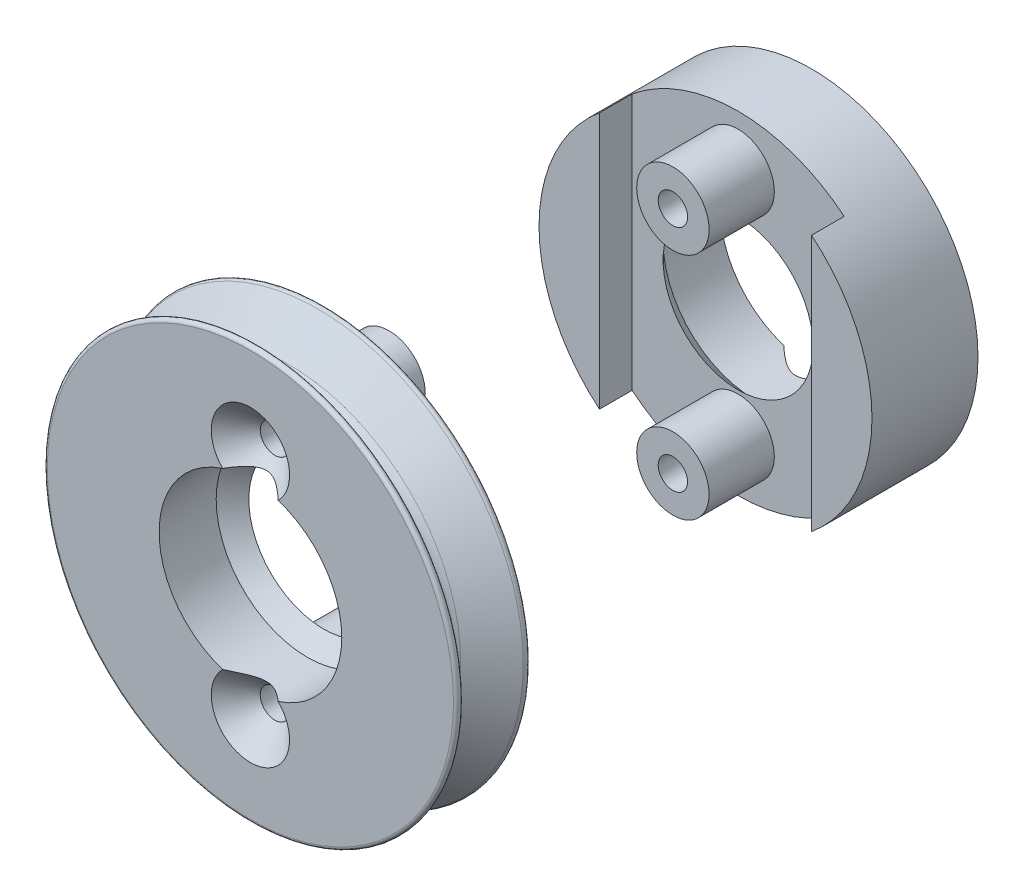
SolidWorks part; units mm, degrees
material "ABS"
ref_plane "Front Plane" through (0, 0, 0) normal (0, 0, 1) x (1, 0, 0)
ref_plane "Top Plane" through (0, 0, 0) normal (0, 1, 0) x (1, 0, 0)
ref_plane "Right Plane" through (0, 0, 0) normal (1, 0, 0) x (0, 0, -1)
sketch "Sketch2" plane through (0, 0, 0) normal (1, 0, 0) x (0, 0, -1)
  line L0 (-2, 11.2) -> (-9, 11.2)
  line L1 (-9, 11.2) -> (-9, 24.9013)
  line L2 (-8.2241, 25.0381) -> (-6.9207, 21.457)
  line L3 (-4.2129, 20.9796) -> (-0.7064, 25.1584)
  line L4 (0, 24.9013) -> (0, 9.2)
  line L6 (-2, 11.2) -> (0, 9.2)
  line L7 (0, 0) -> (7.0902, 0) construction
  arc A0 (-9, 24.9013) -> (-8.2241, 25.0381) centre (-8.6, 24.9013) cw
  arc A1 (-6.9207, 21.457) -> (-4.2129, 20.9796) centre (-5.429, 22) ccw
  arc A2 (-0.7064, 25.1584) -> (0, 24.9013) centre (-0.4, 24.9013) cw
  dimension "D1" = 11.2
  dimension "D4" = 1.5875
  dimension "D7" = 0.4
  dimension "D2" = 7
  dimension "D3" = 40
  dimension "D5" = 2
  dimension "D6" = 45
  dimension "D8" = 20
  dimension "D9" = 22
revolve "Revolve1" add sketch "Sketch2" angle 360 about L7
sketch "Sketch3" plane through (0, 0, 0) normal (0, 0, -1) x (-1, 0, 0)
  line L0 (0, 9.625) -> (0, -9.625) construction
  circle A0 centre (0, 14.0625) radius 4.4375
  circle A1 centre (0, -14.0625) radius 4.4375
  point P4 (0, 18.5)
  point P5 (0, -18.5)
  point P7 (0, -9.625)
  dimension "D1" = 19.25
  dimension "D2" = 37
extrude "Boss-Extrude1" add sketch "Sketch3" along normal blind 8
sketch "Sketch4" plane through (0, 0, -8) normal (0, 0, -1) x (-1, 0, 0)
  circle A0 centre (0, 14.0625) radius 1.8
  circle A1 centre (0, -14.0625) radius 1.8
  dimension "D1" = 3.6
extrude "Cut-Extrude1" cut sketch "Sketch4" against normal through all
chamfer "Chamfer1" distance 3 angle 45 2 edges at (-1.8, -14.0625, 9) (-1.8, 14.0625, 9)
ref_plane "Plane1" through (0, 0, -25.4) normal (0, 0, -1) x (-1, 0, 0)
mirror "Mirror2" about plane through (0, 0, -25.4) normal (0, 0, -1) of bodies 103
sketch "Sketch8" plane through (0, 0, -59.8) normal (0, 0, -1) x (-1, 0, 0)
  circle A0 centre (0, 0) radius 20.4125
  circle A1 centre (0, 0) radius 20.4125 construction
  circle A2 centre (0, 0) radius 31.2181
extrude "Cut-Extrude3" cut sketch "Sketch8" against normal blind 25
sketch "Sketch9" plane through (0, 0, -50.8) normal (0, 0, 1) x (1, 0, 0)
  line L1 (13, -35.7575) -> (-13, -35.7575)
  line L2 (13, -35.7575) -> (13, 35.7575)
  line L3 (13, 35.7575) -> (-13, 35.7575)
  line L4 (-13, -35.7575) -> (-13, 35.7575)
  line L5 (13, -35.7575) -> (-13, 35.7575) construction
  line L6 (13, 35.7575) -> (-13, -35.7575) construction
  line L7 (26.8446, -43.6097) -> (-26.8446, -43.6097)
  line L8 (26.8446, -43.6097) -> (26.8446, 43.6097)
  line L9 (26.8446, 43.6097) -> (-26.8446, 43.6097)
  line L10 (-26.8446, -43.6097) -> (-26.8446, 43.6097)
  line L11 (26.8446, -43.6097) -> (-26.8446, 43.6097) construction
  line L12 (26.8446, 43.6097) -> (-26.8446, -43.6097) construction
  point P0 (0, 0)
  point P5 (0, 0)
  circle M6 centre (0, 0) radius 20.4125
  dimension "D1" = 26
extrude "Boss-Extrude4" add sketch "Sketch9" along normal blind 4 contours L4 M6 | L2 M6 region at (16.0166, 0, -50.8) region at (-16.0166, 0, -50.8)
